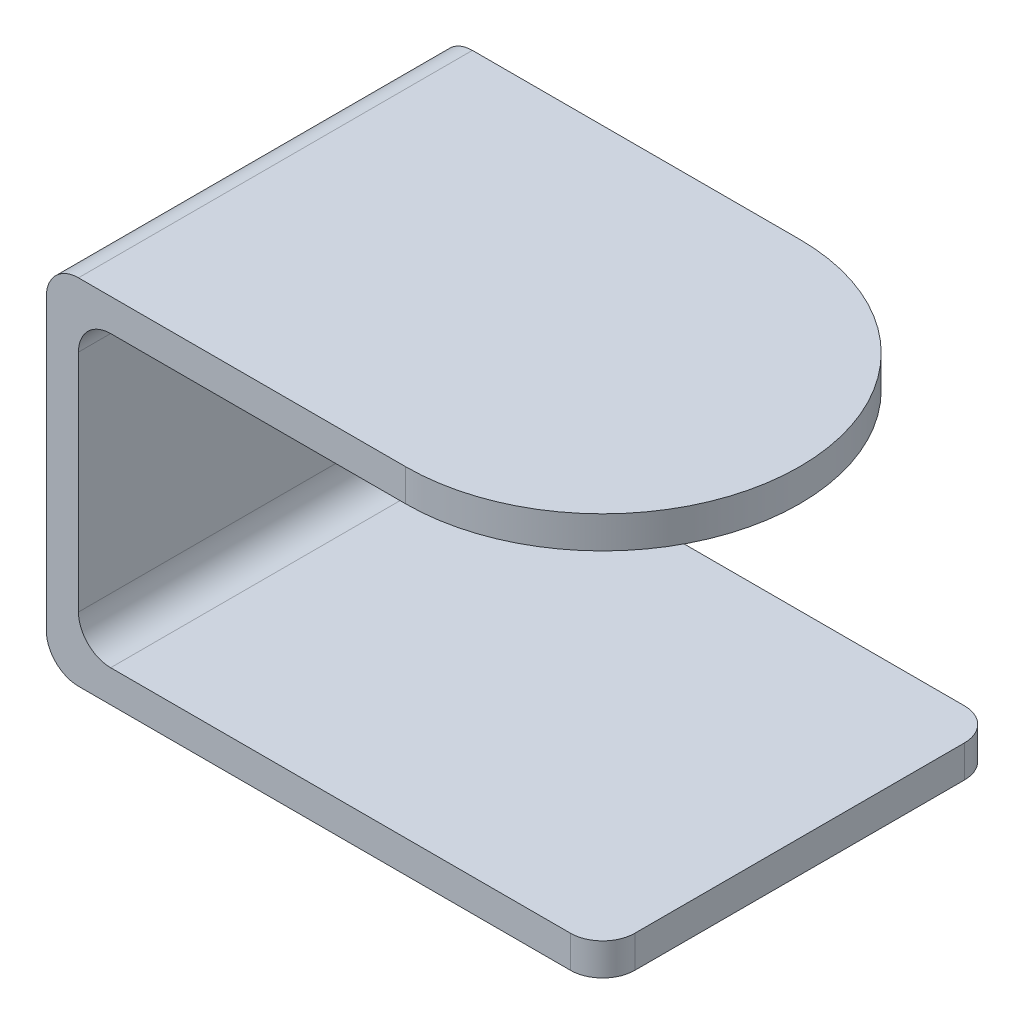
SolidWorks part; units mm, degrees
ref_plane "Front Plane" through (0, 0, 0) normal (0, 0, 1) x (1, 0, 0)
ref_plane "Top Plane" through (0, 0, 0) normal (0, 1, 0) x (1, 0, 0)
ref_plane "Right Plane" through (0, 0, 0) normal (1, 0, 0) x (0, 0, -1)
sketch "Sketch1" plane through (0, 0, 0) normal (0, 0, 1) x (1, 0, 0)
  line L0 (0, 0) -> (-17.3, 0)
  line L1 (-17.3, 0) -> (-17.3, 11)
  line L2 (-17.3, 11) -> (0, 11)
  line L3 (0, 1) -> (-16.3, 1)
  line L4 (-16.3, 1) -> (-16.3, 10)
  line L5 (-16.3, 10) -> (0, 10)
  line L6 (0, 11) -> (0, 10)
  line L7 (0, 1) -> (0, 0)
  dimension "D1" = 17.3
  dimension "D2" = 11
  dimension "D3" = 1
extrude "Boss-Extrude2" add sketch "Sketch1" along normal blind 12.25
fillet "Fillet1" 2 edges at (0, 10.5, 12.25) (0, 10.5, 0) type full round first side face at (-8.4, 5.5, 12.25) second side face at (-8.4, 5.5, 0) middle face at (0, 10.5, 6.125)
fillet "Fillet3" radius 1 6 edges at (0, 0.5, 0) (0, 0.5, 12.25) (-17.3, 0, 6.125) (-16.3, 1, 6.125) (-16.3, 10, 6.125) (-17.3, 11, 6.125)
